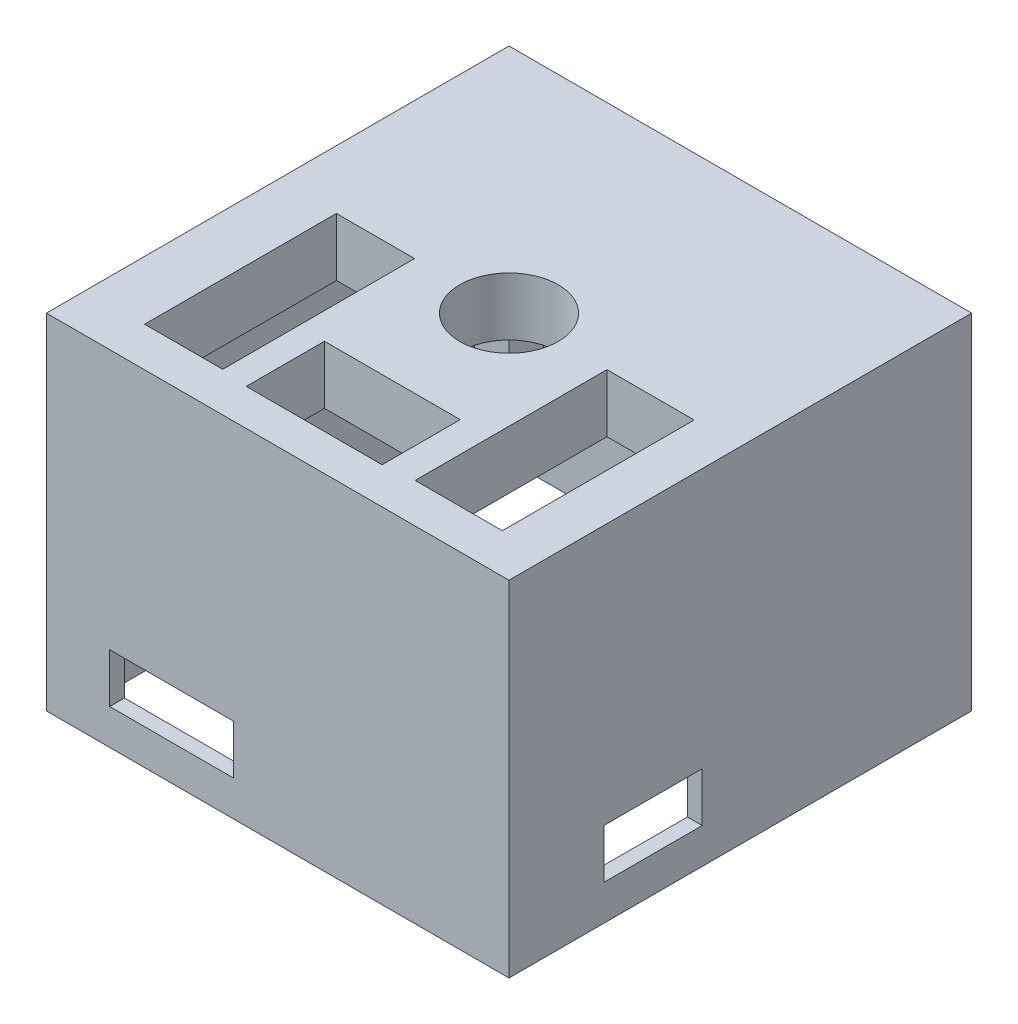
SolidWorks part; units mm, degrees
ref_plane "Front Plane" through (0, 0, 0) normal (0, 0, 1) x (1, 0, 0)
ref_plane "Top Plane" through (0, 0, 0) normal (0, 1, 0) x (1, 0, 0)
ref_plane "Right Plane" through (0, 0, 0) normal (1, 0, 0) x (0, 0, -1)
sketch "Sketch1" plane through (0, 0, 0) normal (0, 1, 0) x (1, 0, 0)
  line L1 (-23.5, -23.5) -> (23.5, -23.5)
  line L2 (-23.5, -23.5) -> (-23.5, 23.5)
  line L3 (-23.5, 23.5) -> (23.5, 23.5)
  line L4 (23.5, -23.5) -> (23.5, 23.5)
  line L5 (-23.5, -23.5) -> (23.5, 23.5) construction
  line L6 (-23.5, 23.5) -> (23.5, -23.5) construction
  point P0 (0, 0)
  dimension "D1" = 47
  dimension "D2" = 47
extrude "Boss-Extrude1" add sketch "Sketch1" along normal blind 32
sketch "Sketch2" plane through (0, 0, 0) normal (0, -1, 0) x (1, 0, 0)
  line L1 (-22, -22) -> (22, -22)
  line L2 (-22, -22) -> (-22, 22)
  line L3 (-22, 22) -> (22, 22)
  line L4 (22, -22) -> (22, 22)
  line L5 (-22, -22) -> (22, 22) construction
  line L6 (-22, 22) -> (22, -22) construction
  point P0 (0, 0)
  dimension "D1" = 44
  dimension "D2" = 44
extrude "Cut-Extrude1" cut sketch "Sketch2" against normal blind 26.1
sketch "Sketch3" plane through (0, 26.1, 0) normal (0, -1, 0) x (1, 0, 0)
  line L0 (-22, 18.5) -> (-18.5, 18.5)
  line L1 (-22, 22) -> (-18.5, 22) construction
  line L2 (-22, 22) -> (-22, 18.5) construction
  line L6 (-18.5, 18.5) -> (-18.5, 22)
  line M6 (22, 22) -> (-22, 22)
  line M7 (-22, 22) -> (-22, -22)
  dimension "D1" = 3.5
  dimension "D2" = 3.5
extrude "Boss-Extrude2" add sketch "Sketch3" along normal blind 20.5 contours M6 M7 region at (-20.25, 26.1, 20.25)
mirror "Mirror1" about plane through (0, 0, 0) normal (1, 0, 0) of "Boss-Extrude2" second plane through (0, 0, 0) second plane normal (0, 0, 1)
sketch "Sketch4" plane through (0, 0, -23.5) normal (0, 0, -1) x (-1, 0, 0)
  line L0 (0, 32) -> (0, 0) construction
  line L1 (-23.5, 32) -> (23.5, 32) construction
  line L121 (15, 3.1573) -> (15, 23.1573)
  line L125 (-15, 3.1573) -> (-15, 23.1573)
  line L126 (-15, 13.1573) -> (-11, 13.1573) construction
  line L132 (-13, 3.1573) -> (-11, 3.1573)
  line L135 (-13, 23.1573) -> (-11, 23.1573)
  line L136 (-13, 23.1573) -> (-13, 3.1573)
  line L137 (-13, 3.1573) -> (-11, 3.1573)
  line L138 (-11, 23.1573) -> (-11, 3.1573)
  point P5 (0, 13.1573)
  dimension "D1" = 30
  dimension "D2" = 20
extrude "Cut-Extrude3" cut sketch "Sketch4" against normal up to next contours L138 L135 L136 L132 region at (12, 13.1573, -23.5)
pattern_linear "LPattern1" count 7 spacing 4 along (-1, 0, 0) of "Cut-Extrude3"
sketch "Sketch8" plane through (0, 0, -23.5) normal (0, 0, -1) x (-1, 0, 0)
  line L2 (-13, 23.1573) -> (-13, 3.1573) construction
  line L3 (-13, 21.1573) -> (13, 21.1573)
  line L4 (-13, 21.1573) -> (-13, 19.1573)
  line L6 (13, 21.1573) -> (13, 19.1573)
  line L7 (13, 23.1573) -> (13, 3.1573) construction
  line L8 (-13, 19.1573) -> (13, 19.1573)
  dimension "D1" = 2
extrude "Boss-Extrude4" add sketch "Sketch8" against normal up to vertex (1.5 mm away) up to point (9, 23.1573, -22)
pattern_linear "LPattern2" count 5 spacing 4 along (0, -1, 0) of "Boss-Extrude4"
sketch "Sketch6" plane through (0, 0, 0) normal (0, -1, 0) x (1, 0, 0)
  line L0 (-23.5, 23.5) -> (-23.5, -23.5)
  line L1 (-23.5, -23.5) -> (23.5, -23.5)
  line L2 (23.5, -23.5) -> (23.5, 23.5)
  line L3 (23.5, 23.5) -> (-23.5, 23.5)
  line L9 (-22, 22) -> (22, 22)
  line L10 (-22, 22) -> (-22, -22)
  line L11 (-22, -22) -> (22, -22)
  line L12 (22, 22) -> (22, -22)
extrude "Boss-Extrude5" add sketch "Sketch6" along normal blind 3
sketch "Sketch7" plane through (0, 32, 0) normal (0, 1, 0) x (1, 0, 0)
  circle A0 centre (0, 0) radius 5
  dimension "D1" = 10
extrude "Cut-Extrude4" cut sketch "Sketch7" against normal blind 10
sketch "Sketch9" plane through (-23.5, 0, 0) normal (-1, 0, 0) x (0, 0, 1)
sketch "Sketch10" plane through (-23.5, 0, 0) normal (-1, 0, 0) x (0, 0, 1)
  line L1 (13.8718, 0.6) -> (3.8718, 0.6)
  line L2 (13.8718, 0.6) -> (13.8718, 5.6)
  line L3 (13.8718, 5.6) -> (3.8718, 5.6)
  line L4 (3.8718, 0.6) -> (3.8718, 5.6)
  dimension "D1" = 10
  dimension "D2" = 5
extrude "Cut-Extrude5" cut sketch "Sketch10" against normal through all
sketch "Sketch12" plane through (0, 0, 23.5) normal (0, 0, 1) x (1, 0, 0)
  line L0 (-22.204, 0.6) -> (20.7721, 0.6) construction
  line L1 (-4.4975, 0.6) -> (-17.0688, 0.6)
  line L2 (-4.4975, 0.6) -> (-4.4975, 5.6)
  line L3 (-4.4975, 5.6) -> (-17.0688, 5.6)
  line L4 (-17.0688, 0.6) -> (-17.0688, 5.6)
  line L5 (-16.4228, 5.6) -> (-19.3228, 5.6) construction
extrude "Cut-Extrude6" cut sketch "Sketch12" against normal blind 10
sketch "Sketch13" plane through (0, 32, 0) normal (0, 1, 0) x (1, 0, 0)
  line L1 (-17.5335, 0) -> (-9.5934, 0)
  line L2 (-17.5335, 0) -> (-17.5335, -19.4859)
  line L3 (-17.5335, -19.4859) -> (-9.5934, -19.4859)
  line L4 (-9.5934, 0) -> (-9.5934, -19.4859)
  line L5 (18.8079, 0) -> (9.9516, 0)
  line L6 (18.8079, 0) -> (18.8079, -19.4859)
  line L7 (18.8079, -19.4859) -> (9.9516, -19.4859)
  line L8 (9.9516, 0) -> (9.9516, -19.4859)
  line L9 (-6.8977, -19.7913) -> (6.8977, -19.7913)
  line L10 (-6.8977, -19.7913) -> (-6.8977, -11.8512)
  line L11 (-6.8977, -11.8512) -> (6.8977, -11.8512)
  line L12 (6.8977, -19.7913) -> (6.8977, -11.8512)
  line L13 (-6.8977, -19.7913) -> (6.8977, -11.8512) construction
  line L14 (-6.8977, -11.8512) -> (6.8977, -19.7913) construction
  point P8 (0, -15.8213)
extrude "Cut-Extrude7" cut sketch "Sketch13" against normal blind 10
